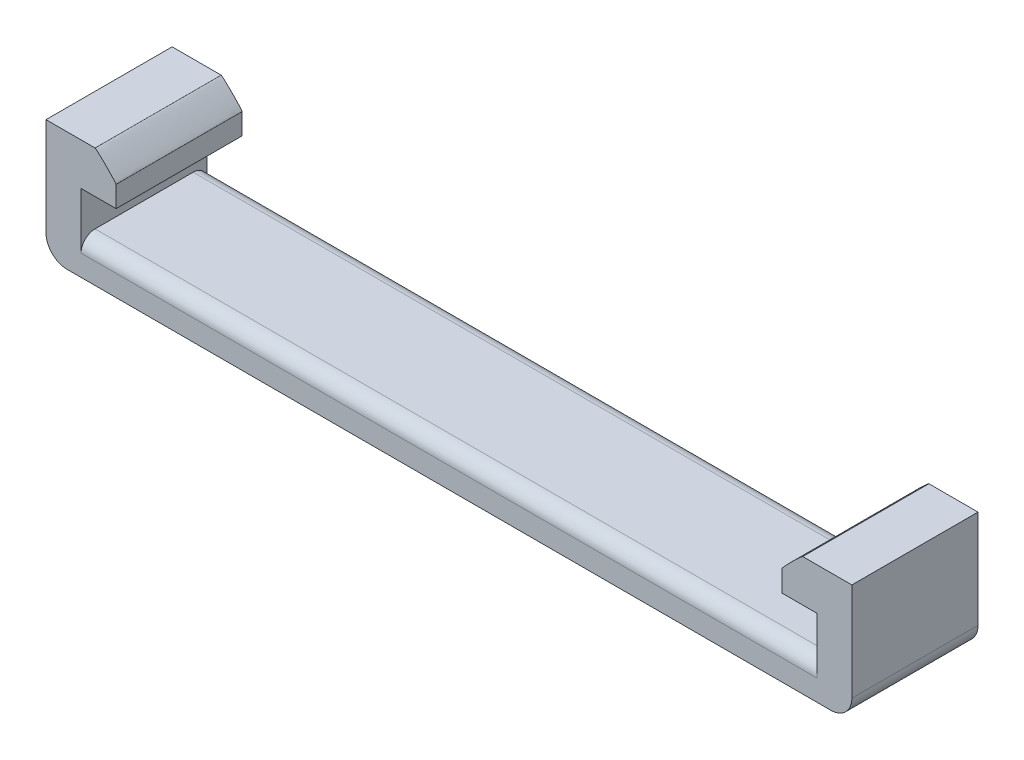
SolidWorks part; units mm, degrees
ref_plane "Front Plane" through (0, 0, 0) normal (0, 0, 1) x (1, 0, 0)
ref_plane "Top Plane" through (0, 0, 0) normal (0, 1, 0) x (1, 0, 0)
ref_plane "Right Plane" through (0, 0, 0) normal (1, 0, 0) x (0, 0, -1)
sketch "Sketch1" plane through (0, 0, 0) normal (0, 1, 0) x (1, 0, 0)
  line L1 (0, 0) -> (23, 0)
  line L2 (0, 0) -> (0, -3.6)
  line L3 (0, -3.6) -> (23, -3.6)
  line L4 (23, 0) -> (23, -3.6)
  dimension "D1" = 3.6
  dimension "D2" = 23
extrude "Boss-Extrude1" add sketch "Sketch1" along normal blind 1
sketch "Sketch2" plane through (0, 1, 0) normal (0, 1, 0) x (1, 0, 0)
  line L0 (0, -3.6) -> (23, -3.6) construction
  line L1 (0, 0) -> (1, 0)
  line L2 (0, 0) -> (0, -3.6)
  line L3 (0, -3.6) -> (1, -3.6)
  line L4 (1, 0) -> (1, -3.6)
  line L5 (23, 0) -> (0, 0) construction
  line L6 (23, -3.6) -> (22, -3.6)
  line L7 (23, -3.6) -> (23, 0)
  line L8 (23, 0) -> (22, 0)
  line L9 (22, -3.6) -> (22, 0)
  dimension "D1" = 1
  dimension "D2" = 1
extrude "Boss-Extrude2" add sketch "Sketch2" along normal blind 2.4
sketch "Sketch3" plane through (0, 0, 3.6) normal (0, 0, 1) x (1, 0, 0)
  line L1 (1, 3.4) -> (2, 3.4)
  line L2 (1, 3.4) -> (1, 2.2)
  line L3 (1, 2.2) -> (2, 2.2)
  line L4 (2, 3.4) -> (2, 2.2)
  line L5 (22, 3.4) -> (21, 3.4)
  line L6 (22, 3.4) -> (22, 2.2)
  line L7 (22, 2.2) -> (21, 2.2)
  line L8 (21, 3.4) -> (21, 2.2)
  dimension "D1" = 1
  dimension "D2" = 1
  dimension "D3" = 1.2
  dimension "D4" = 1.2
extrude "Boss-Extrude3" add sketch "Sketch3" against normal blind 3.6
fillet "Fillet1" radius 0.6 2 edges at (21, 3.4, 1.8) (2, 3.4, 1.8) conic rho 0.05
fillet "Fillet2" radius 0.6 2 edges at (23, 0, 1.8) (0, 0, 1.8)
fillet "Fillet3" radius 0.4 2 edges at (11.5, 1, 0) (11.5, 1, 3.6)
